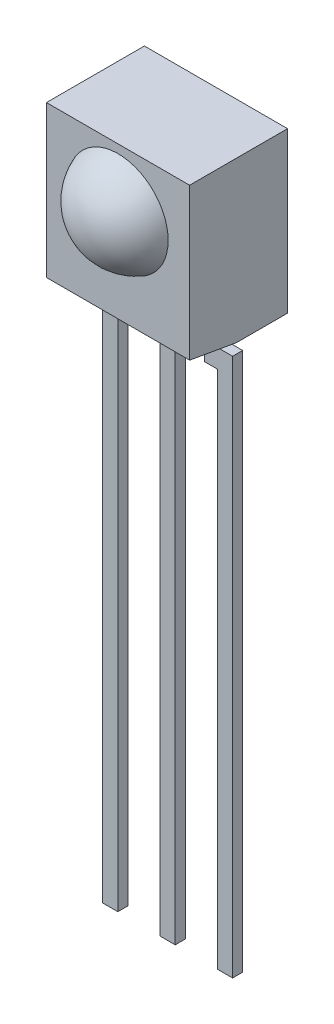
SolidWorks part; units mm, degrees
ref_plane "Front Plane" through (0, 0, 0) normal (0, 0, 1) x (1, 0, 0)
ref_plane "Top Plane" through (0, 0, 0) normal (0, 1, 0) x (1, 0, 0)
ref_plane "Right Plane" through (0, 0, 0) normal (1, 0, 0) x (0, 0, -1)
sketch "Sketch1" plane through (0, 0, 0) normal (0, 0, 1) x (1, 0, 0)
  line L1 (3.055, -3.41) -> (-3.055, -3.41)
  line L2 (3.055, -3.41) -> (3.055, 3.41)
  line L3 (3.055, 3.41) -> (-3.055, 3.41)
  line L4 (-3.055, -3.41) -> (-3.055, 3.41)
  line L5 (3.055, -3.41) -> (-3.055, 3.41) construction
  line L6 (3.055, 3.41) -> (-3.055, -3.41) construction
  point P0 (0, 0)
  dimension "D1" = 6.11
  dimension "D2" = 6.82
extrude "Boss-Extrude1" add sketch "Sketch1" along normal blind 4.18
sketch "Sketch3" plane through (0, 0, 0) normal (1, 0, 0) x (0, 0, -1)
  line L0 (-3.405, 3.185) -> (-3.405, -1.365)
  line L1 (-4.18, 3.41) -> (0, 3.41) construction
  line L2 (-4.18, -3.41) -> (-4.18, 3.41) construction
  arc A0 (-3.405, 3.185) -> (-3.405, -1.365) centre (-3.405, 0.91) ccw
  point P6 (-5.68, 0.91)
  dimension "D1" = 4.55
  dimension "D2" = 1.5
  dimension "2.5" = 2.5
revolve "Revolve1" add sketch "Sketch3" angle 360 about L0
sketch "Sketch4" plane through (0, -3.41, 0) normal (0, -1, 0) x (1, 0, 0)
  line L0 (-3.055, 1.85) -> (3.055, 1.85) construction
  line L1 (-3.055, 4.18) -> (-3.055, 0) construction
  line L2 (3.055, 4.18) -> (3.055, 0) construction
  line L3 (-3.055, 4.18) -> (3.055, 4.18) construction
  line L5 (0.325, 1.635) -> (-0.325, 1.635)
  line L6 (0.325, 1.635) -> (0.325, 2.065)
  line L7 (0.325, 2.065) -> (-0.325, 2.065)
  line L8 (-0.325, 1.635) -> (-0.325, 2.065)
  line L9 (0.325, 1.635) -> (-0.325, 2.065) construction
  line L10 (0.325, 2.065) -> (-0.325, 1.635) construction
  point P8 (0, 1.85)
  dimension "D1" = 2.33
  dimension "D2" = 0.43
  dimension "D3" = 0.65
extrude "Boss-Extrude2" add sketch "Sketch4" along normal blind 1.5
pattern_linear "LPattern1" count 2 spacing 1.9 along (1, 0, 0) count 2 spacing 1.9 along (-1, 0, 0) of "Boss-Extrude2" pattern seed only yes
sketch "Sketch5" plane through (-2.225, 0, 0) normal (-1, 0, 0) x (0, 0, 1)
  line L0 (2.065, -4.91) -> (2.065, -3.41) construction
  line L1 (1.635, -4.91) -> (2.065, -4.91)
  line L2 (1.635, -4.91) -> (1.635, -4.11)
  line L3 (1.635, -4.11) -> (2.065, -4.11)
  line L4 (2.065, -4.91) -> (2.065, -4.11)
  dimension "D1" = 0.8
extrude "Boss-Extrude3" add sketch "Sketch5" along normal blind 0.55
mirror "Mirror1" about plane through (0, 0, 0) normal (1, 0, 0) of "Boss-Extrude3"
ref_plane "Plane1" through (0, -27.09, 0) normal (0, 1, 0) x (1, 0, 0)
sketch "Sketch6" plane through (0, -4.91, 0) normal (0, -1, 0) x (1, 0, 0)
  line L0 (-1.575, 2.065) -> (-2.775, 2.065) construction
  line L1 (0.325, 1.635) -> (-0.325, 1.635)
  line L2 (0.325, 1.635) -> (0.325, 2.065)
  line L3 (0.325, 2.065) -> (-0.325, 2.065)
  line L4 (-0.325, 1.635) -> (-0.325, 2.065)
  line L5 (-2.775, 1.635) -> (-2.125, 1.635)
  line L6 (-2.775, 1.635) -> (-2.775, 2.065)
  line L7 (-2.775, 2.065) -> (-2.125, 2.065)
  line L8 (-2.125, 1.635) -> (-2.125, 2.065)
  line L9 (2.775, 2.065) -> (1.575, 2.065) construction
  line L10 (2.775, 1.635) -> (2.125, 1.635)
  line L11 (2.775, 1.635) -> (2.775, 2.065)
  line L12 (2.775, 2.065) -> (2.125, 2.065)
  line L13 (2.125, 1.635) -> (2.125, 2.065)
  dimension "D1" = 0.65
  dimension "D2" = 0.65
extrude "Boss-Extrude4" add sketch "Sketch6" along normal blind 5
chamfer "Chamfer1" distance 2 angle 10 1 edges at (0, -3.41, 4.18) first distance on face at (1.9, -3.41, 1.85)
sketch "Sketch7" plane through (0, -9.91, 0) normal (0, -1, 0) x (1, 0, 0)
  line L1 (-0.325, 1.635) -> (0.325, 1.635)
  line L2 (-0.325, 1.635) -> (-0.325, 2.065)
  line L3 (-0.325, 2.065) -> (0.325, 2.065)
  line L4 (0.325, 1.635) -> (0.325, 2.065)
  line L5 (-2.125, 1.635) -> (-2.775, 1.635)
  line L6 (-2.125, 1.635) -> (-2.125, 2.065)
  line L7 (-2.125, 2.065) -> (-2.775, 2.065)
  line L8 (-2.775, 1.635) -> (-2.775, 2.065)
  line L9 (-2.775, 2.065) -> (-2.775, 1.635) construction
  line L10 (2.775, 1.635) -> (2.125, 1.635)
  line L11 (2.775, 1.635) -> (2.775, 2.065)
  line L12 (2.775, 2.065) -> (2.125, 2.065)
  line L13 (2.125, 1.635) -> (2.125, 2.065)
  line L14 (-2.125, 2.065) -> (-2.775, 2.065) construction
  line L15 (2.125, 1.635) -> (2.775, 1.635) construction
  line L16 (2.775, 1.635) -> (2.775, 2.065) construction
extrude "Boss-Extrude5" add sketch "Sketch7" along normal up to surface (17.18 mm away) up to plane "Plane1"
